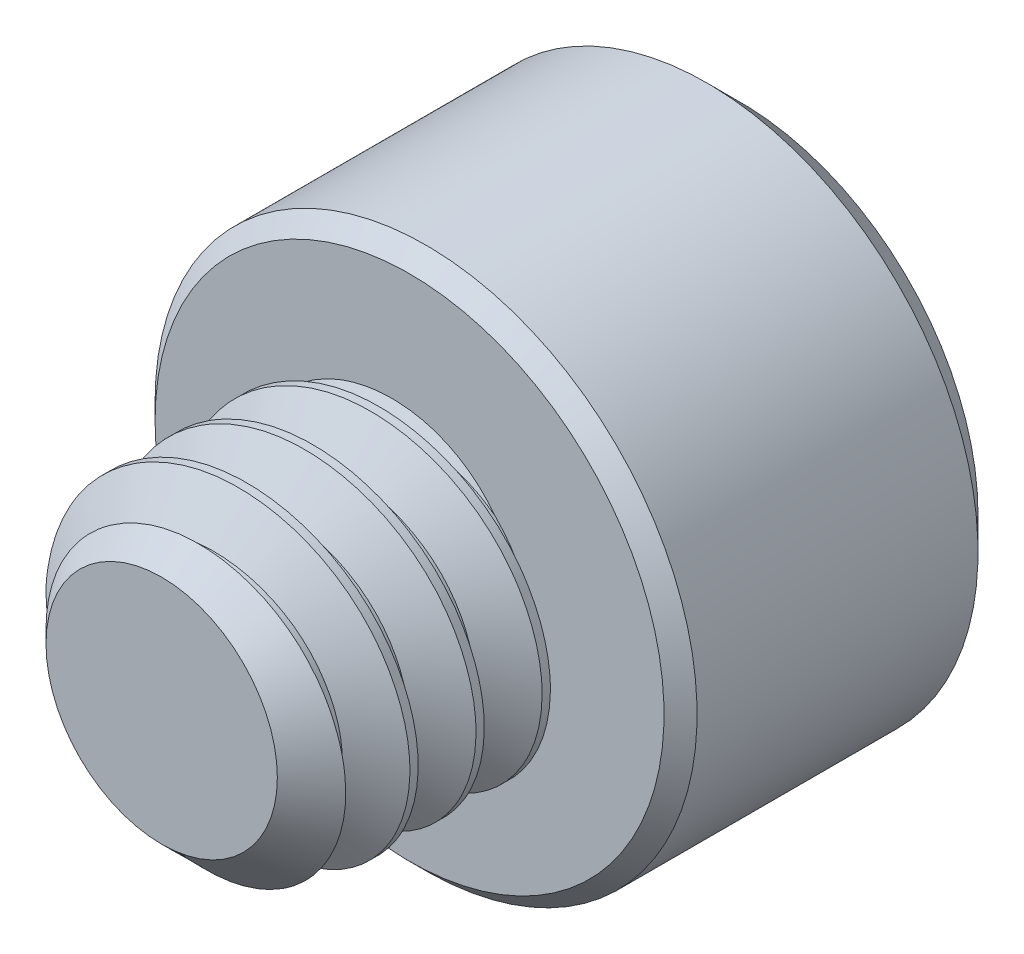
SolidWorks part; units mm, degrees
ref_plane "Front Plane" through (0, 0, 0) normal (0, 0, 1) x (1, 0, 0)
ref_plane "Top Plane" through (0, 0, 0) normal (0, 1, 0) x (1, 0, 0)
ref_plane "Right Plane" through (0, 0, 0) normal (1, 0, 0) x (0, 0, -1)
sketch "Sketch1" plane through (0, 0, 0) normal (0, 0, 1) x (1, 0, 0)
  line L0 (0, 1.5875) -> (0, -1.5875) construction
  circle A0 centre (0, 0) radius 1.5875
  dimension "OD" = 3.175
extrude "Extrude1" add sketch "Sketch1" against normal blind 2.3813
sketch "Sketch2" plane through (0, 0, 0) normal (0, 0, 1) x (1, 0, 0)
  circle A0 centre (0, 0) radius 1.5875 construction
  circle A1 centre (0, 0) radius 1.5875
curve "Helix/Spiral1" pitch 0.635 height 3.0163 radius 1.5875 centre (0, 0, 0) axis (0, 0, -1) start towards (0, 1, 0) parameters "pitch"=0.635
chamfer "Chamfer3" distance 0.4763 angle 45 1 edges at (1.5875, 0, 0)
sketch "Sketch3" plane through (0, 0, 0) normal (1, 0, 0) x (0, 0, -1)
  line L0 (-0.5556, 1.5875) -> (-0.3175, 1.1751)
  line L1 (-0.3175, 1.1751) -> (-0.2381, 1.1751)
  line L2 (-0.2381, 1.1751) -> (0, 1.5875)
  line L3 (-0.5556, 1.5875) -> (0, 1.5875)
  line L4 (-0.2778, 1.5875) -> (-0.2778, 1.1751) construction
  line L5 (-0.4366, 1.3813) -> (-0.1191, 1.3813) construction
  line L6 (0, 1.5875) -> (0, -1.5875) construction
  dimension "D2" = 0.3175
  dimension "D3" = 60
sweep "Cut-Sweep1" cut profiles "Sketch3" path "Helix/Spiral1"
sketch "Sketch6" plane through (0, 0, -2.3813) normal (0, 0, -1) x (-1, 0, 0)
  circle A0 centre (0, 0) radius 2.6035
  dimension "head dia" = 5.207
extrude "Extrude2" add sketch "Sketch6" along normal blind 3.175
sketch "Sketch7" plane through (0, 0, -5.5563) normal (0, 0, -1) x (-1, 0, 0)
  line L1 (0, 1.3748) -> (-1.1906, 0.6874)
  line L2 (-1.1906, 0.6874) -> (-1.1906, -0.6874)
  line L3 (-1.1906, -0.6874) -> (0, -1.3748)
  line L4 (0, -1.3748) -> (1.1906, -0.6874)
  line L5 (1.1906, -0.6874) -> (1.1906, 0.6874)
  line L6 (1.1906, 0.6874) -> (0, 1.3748)
  circle A0 centre (0, 0) radius 1.1906 construction
  dimension "hex dia" = 2.3813
extrude "Cut-Extrude1" cut sketch "Sketch7" against normal blind 1.7859
sketch "Sketch8" plane through (0, 0, -5.5563) normal (0, 0, -1) x (-1, 0, 0)
  circle A0 centre (0, 0) radius 1.3748
extrude "Cut-Extrude2" cut sketch "Sketch8" against normal blind 0.3175 draft 45
chamfer "Chamfer1" distance 0.3175 angle 45 1 edges at (-2.6035, 0, -5.5563)
chamfer "Chamfer2" distance 0.1588 angle 45 1 edges at (-2.6035, 0, -2.3813)
equation "\"D3@Helix/Spiral1\" = \"screw length@Extrude1\"+\"pitch@Helix/Spiral1\""
equation "\"D1@Sketch3\" = \"pitch@Helix/Spiral1\"*.125"
equation "\"D2@Sketch3\" = \"pitch@Helix/Spiral1\"*.5"
equation "\"D1@Cut-Extrude1\" = \"hex dia@Sketch7\"*.75"
equation "\"D1@Chamfer1\" = \"head depth@Extrude2\"/10"
equation "\"D1@Sketch9\" = \"pitch@Helix/Spiral1\"*5.5"
equation "\"D1@Chamfer2\" = \"D1@Chamfer1\"/2"
equation "\"D1@Cut-Extrude2\" = \"D1@Chamfer2\"*2"
equation "\"D1@Chamfer3\" = \"pitch@Helix/Spiral1\"*.750"
equation "\"D2@Sketch9\" = \"head depth@Extrude2\""
equation "\"D3@Sketch9\" = \"head dia@Sketch6\""
equation "\"D4@Sketch9\" = \"screw length@Extrude1\""
